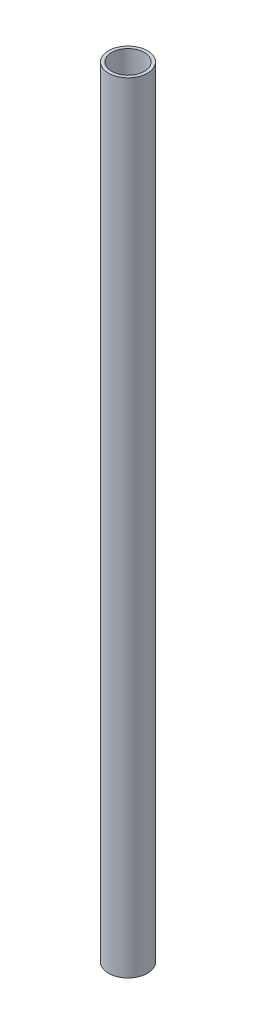
SolidWorks part; units mm, degrees
ref_plane "Front Plane" through (0, 0, 0) normal (0, 0, 1) x (1, 0, 0)
ref_plane "Top Plane" through (0, 0, 0) normal (0, 1, 0) x (1, 0, 0)
ref_plane "Right Plane" through (0, 0, 0) normal (1, 0, 0) x (0, 0, -1)
sketch "Sketch1" plane through (0, 0, 0) normal (0, 1, 0) x (1, 0, 0)
  circle A0 centre (0, 0) radius 12.5
  circle A1 centre (0, 0) radius 10.5
  dimension "D1" = 25
  dimension "D2" = 21
extrude "Boss-Extrude1" add sketch "Sketch1" along normal blind 500
equation "\"D1@Sketch1\" = \"cf_tube_outer_diameter\""
equation "\"D1@Boss-Extrude1\"= \"mid_tube_length\""
equation "\"cf_tube_outer_diameter\" = 25mm"
equation "\"mid_plate_mid_to_top\" = 100mm"
equation "\"mid_plate_mid_to_bottom\" = 30mm"
equation "\"mid_plate_horizontal_spacing\" = 250mm"
equation "\"mid_tube_length\" = 500mm"
equation "\"cf_tube_inner_diameter\" = 21mm"
equation "\"D2@Sketch1\"=\"cf_tube_inner_diameter\""
